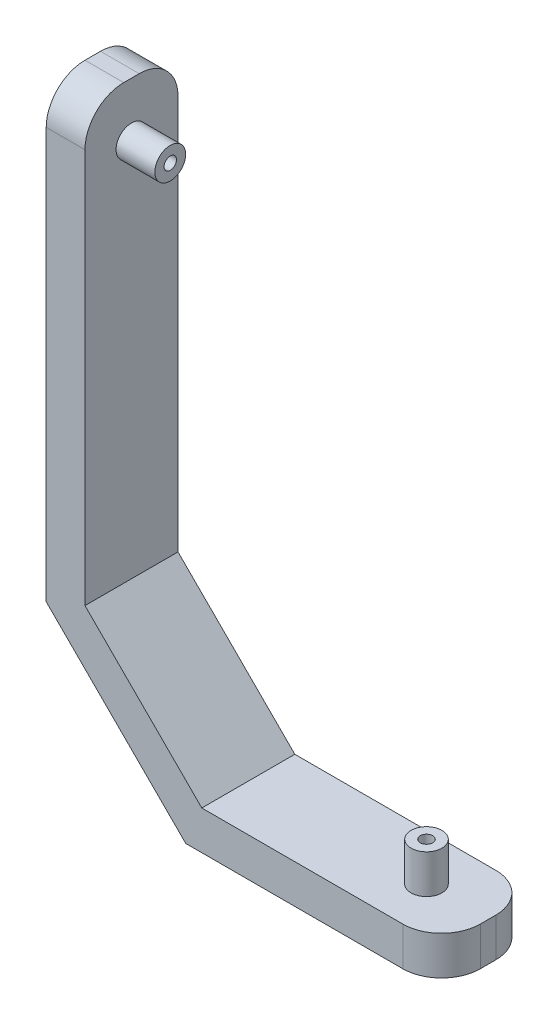
SolidWorks part; units mm, degrees
ref_plane "Front Plane" through (0, 0, 0) normal (0, 0, 1) x (1, 0, 0)
ref_plane "Top Plane" through (0, 0, 0) normal (0, 1, 0) x (1, 0, 0)
ref_plane "Right Plane" through (0, 0, 0) normal (1, 0, 0) x (0, 0, -1)
sketch "Sketch11" plane through (0, 0, 0) normal (0, 0, 1) x (1, 0, 0)
  line L0 (-76.2, 30.1421) -> (-46.0579, 0)
  line L1 (-76.2, 142) -> (-86.2, 142)
  line L2 (-76.2, 142) -> (-76.2, 26)
  line L3 (-76.2, 26) -> (-86.2, 26)
  line L4 (-86.2, 142) -> (-86.2, 26)
  line L5 (15.8, 0) -> (-50.2, 0)
  line L6 (15.8, 0) -> (15.8, -10)
  line L7 (15.8, -10) -> (-50.2, -10)
  line L8 (-50.2, 0) -> (-50.2, -10)
  line L9 (-50.2, -10) -> (-86.2, 26)
  dimension "D1" = 10
  dimension "D2" = 102
  dimension "D3" = 152
  dimension "D4" = 45
  dimension "D5" = 10
  dimension "D6" = 10
  dimension "D7" = 66
  dimension "D8" = 15.8
extrude "Boss-Extrude7" add sketch "Sketch11" against normal blind 12 and the other way blind 12 contours L9 L8 L5 L0 L2 L3 | L1 L4 L2 | L7 L6 L5 L8 region at (-81.2, 84, 0) region at (-64.8264, 11.3736, 0)
fillet "Fillet1" radius 10 4 edges at (-81.2, 142, -12) (15.8, -5, -12) (15.8, -5, 12) (-81.2, 142, 12)
sketch "Sketch1" plane through (-76.2, 0, 0) normal (1, 0, 0) x (0, 0, -1)
  line L0 (2, 142) -> (-2, 142) construction
  circle A1 centre (0, 128) radius 3.98
  point P6 (0, 142)
  dimension "D1" = 14
  dimension "D2" = 7.96
extrude "Boss-Extrude3" add sketch "Sketch1" along normal blind 10
sketch "Sketch5" plane through (-66.2, 0, 0) normal (1, 0, 0) x (0, 0, -1)
  circle A0 centre (0, 128) radius 1.6
  circle A1 centre (0, 128) radius 3.98 construction
  dimension "D1" = 3.2
extrude "Cut-Extrude1" cut sketch "Sketch5" against normal through all
sketch "Sketch6" plane through (-86.2, 0, 0) normal (-1, 0, 0) x (0, 0, 1)
  circle A0 centre (0, 128) radius 2
  circle A1 centre (0, 128) radius 1.6 construction
extrude "Cut-Extrude2" cut sketch "Sketch6" against normal blind 3
sketch "Sketch7" plane through (0, 0, 0) normal (0, 1, 0) x (1, 0, 0)
  line L0 (15.8, 2) -> (15.8, -2) construction
  circle A1 centre (-0.0882, 0) radius 3.98
  point P5 (15.8, 0)
  dimension "D1" = 7.96
  dimension "D2" = 15.8882
extrude "Boss-Extrude5" add sketch "Sketch7" along normal blind 10
sketch "Sketch9" plane through (0, 10, 0) normal (0, 1, 0) x (1, 0, 0)
  circle A0 centre (-0.0882, 0) radius 1.6
  dimension "D1" = 3.2
extrude "Cut-Extrude3" cut sketch "Sketch9" against normal blind 17
sketch "Sketch10" plane through (0, -10, 0) normal (0, -1, 0) x (1, 0, 0)
  circle A0 centre (-0.0882, 0) radius 4
  dimension "D1" = 8
extrude "Cut-Extrude4" cut sketch "Sketch10" against normal blind 3
sketch "Sketch12" plane through (0, 0, 0) normal (0, 0, 1) x (1, 0, 0)
  line L0 (0, 0) -> (-76.2, 0)
  line L1 (-76.2, 0) -> (-76.2, 128)
  line L2 (-76.2, 124.02) -> (-76.2, 131.98) construction
